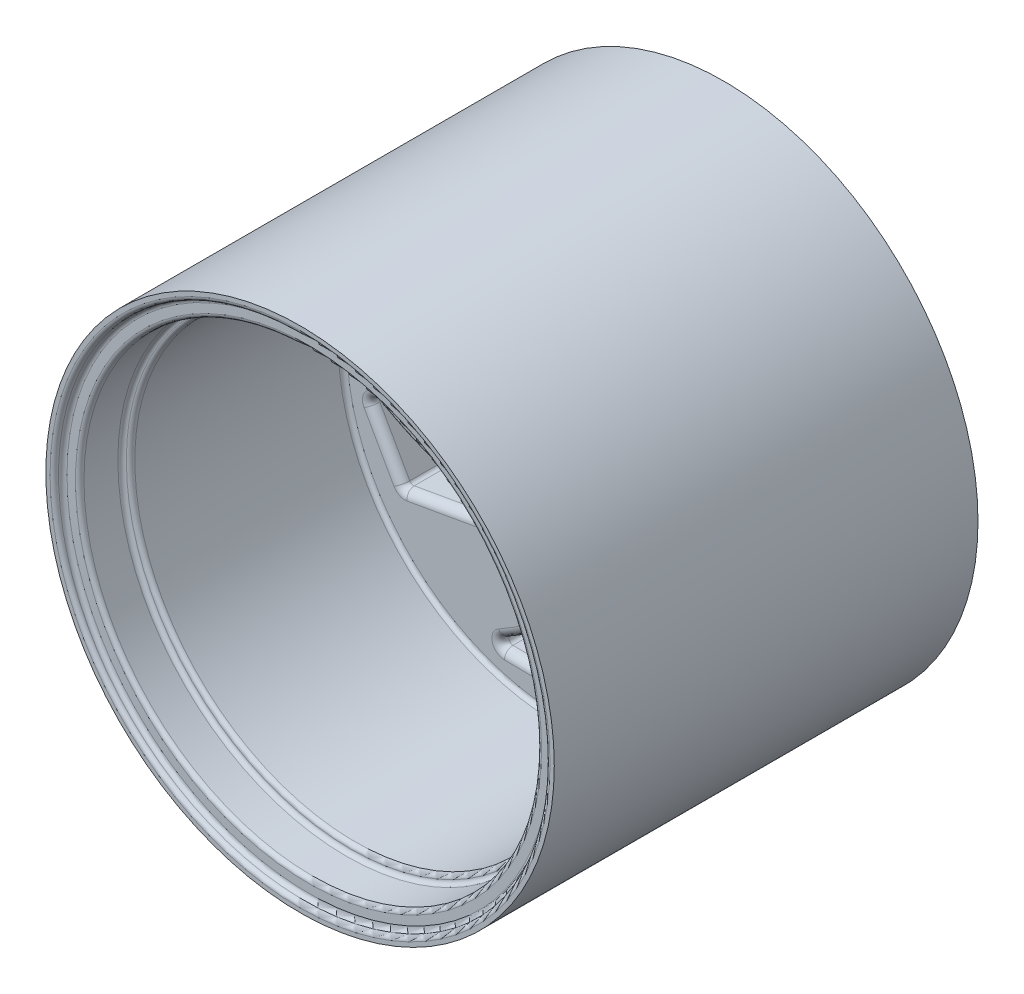
SolidWorks part; units mm, degrees
ref_plane "Ön Düzlem" through (0, 0, 0) normal (0, 0, 1) x (1, 0, 0)
ref_plane "Üst Düzlem" through (0, 0, 0) normal (0, 1, 0) x (1, 0, 0)
ref_plane "Sağ Düzlem" through (0, 0, 0) normal (1, 0, 0) x (0, 0, -1)
sketch "Çizim1" plane through (0, 0, 0) normal (0, 0, 1) x (1, 0, 0)
  circle A0 centre (-8.1488, -1.5541) radius 30
  dimension "D1" = 60
extrude "Yükseklik-Ekstrüzyon1" add sketch "Çizim1" along normal blind 50
sketch "Çizim2" plane through (0, 0, 0) normal (0, 0, -1) x (-1, 0, 0)
  circle A0 centre (8.1488, -1.5541) radius 29
  circle A1 centre (8.1488, -1.5541) radius 30 construction
  dimension "D1" = 1
extrude "Kes-Ekstrüzyon1" cut sketch "Çizim2" against normal blind 1
sketch "Çizim3" plane through (0, 0, 50) normal (0, 0, 1) x (1, 0, 0)
  circle A0 centre (-8.1488, -1.5541) radius 29
  circle A1 centre (-8.1488, -1.5541) radius 30 construction
  dimension "D1" = 1
extrude "Kes-Ekstrüzyon2" cut sketch "Çizim3" against normal blind 1
sketch "Çizim4" plane through (0, 0, 49) normal (0, 0, 1) x (1, 0, 0)
  circle A0 centre (-8.1488, -1.5541) radius 27
  circle A1 centre (-8.1488, -1.5541) radius 29 construction
  dimension "D1" = 2
extrude "Kes-Ekstrüzyon3" cut sketch "Çizim4" against normal blind 5
sketch "Çizim5" plane through (0, 0, 44) normal (0, 0, 1) x (1, 0, 0)
  circle A0 centre (-8.1488, -1.5541) radius 26
  circle A1 centre (-8.1488, -1.5541) radius 27 construction
  dimension "D1" = 1
extrude "Kes-Ekstrüzyon4" cut sketch "Çizim5" against normal blind 25
sketch "Çizim6" plane through (0, 0, 19) normal (0, 0, 1) x (1, 0, 0)
  circle A0 centre (-8.1488, -1.5541) radius 10
  circle A1 centre (-8.1488, -1.5541) radius 8
  circle A2 centre (-8.1488, 4.4459) radius 1
  circle A3 centre (-3.9061, 2.6885) radius 1
  circle A4 centre (-2.1488, -1.5541) radius 1
  circle A5 centre (-3.9061, -5.7967) radius 1
  circle A6 centre (-8.1488, -7.5541) radius 1
  circle A7 centre (-12.3914, -5.7967) radius 1
  circle A8 centre (-14.1488, -1.5541) radius 1
  circle A9 centre (-12.3914, 2.6885) radius 1
  point P23 (-8.1488, -1.5541)
  dimension "D1" = 20
  dimension "D2" = 2
  dimension "D3" = 2
  dimension "D4" = 6
  dimension "D5" = 8
ref_axis "Eksen1" through (-8.1488, -1.5541, 50) along (0, 0, -1)
extrude "Yükseklik-Ekstrüzyon2" add sketch "Çizim6" along normal blind 2 contours A0 A1 | A2 | A8 | A7 | A6 | A5 | A3 | A9 | A4 region at (-17.8659, -1.5541, 19) region at (-8.1488, 4.4459, 19) region at (-3.9061, 2.6885, 19) region at (-3.9061, -5.7967, 19) region at (-8.1488, -7.5541, 19) region at (-12.3914, -5.7967, 19) region at (-14.1488, -1.5541, 19)
sketch "Çizim8" plane through (0, 0, 19) normal (0, 0, 1) x (1, 0, 0)
  circle A0 centre (-8.1488, -1.5541) radius 2
  dimension "D1" = 4
extrude "Kes-Ekstrüzyon5" cut sketch "Çizim8" against normal through all
sketch "Çizim9" plane through (0, 0, 19) normal (0, 0, 1) x (1, 0, 0)
  line L0 (-13.9257, 6.6084) -> (-8.8336, 20.6384)
  line L1 (-8.8336, 20.6384) -> (0.7231, 20.5255)
  line L3 (-3.9683, 7.5301) -> (10.7281, 10.1352)
  line L4 (10.7281, 10.1352) -> (15.4086, 1.8024)
  line L5 (1.8086, -0.6324) -> (11.4129, -12.0573)
  line L6 (11.4129, -12.0573) -> (6.5368, -20.2771)
  line L7 (-2.3718, -9.7166) -> (-7.464, -23.7466)
  line L8 (-7.464, -23.7466) -> (-17.0206, -23.6337)
  line L9 (-12.3293, -10.6383) -> (-27.0257, -13.2434)
  line L10 (-27.0257, -13.2434) -> (-31.7062, -4.9106)
  line L11 (-18.1062, -2.4758) -> (-27.7105, 8.9491)
  line L12 (-30.8072, 6.6742) -> (-25.9311, 14.894) [skipped]
  line L13 (-21.203, -4.7508) -> (-30.8072, 6.6742) [skipped]
  line L14 (-29.7006, -19.3377) -> (-34.3811, -11.0049) [skipped]
  line L15 (-15.0042, -16.7326) -> (-29.7006, -19.3377) [skipped]
  line L16 (-1.5282, -17.3553) -> (-6.6204, -31.3853) [skipped]
  line L17 (-6.6204, -31.3853) -> (-16.177, -31.2724) [skipped]
  line L18 (5.749, -5.9961) -> (15.3533, -17.421) [skipped]
  line L19 (15.3533, -17.421) -> (10.4771, -25.6408) [skipped]
  line L20 (-0.4498, 5.9858) -> (14.2467, 8.5908) [skipped]
  line L21 (14.2467, 8.5908) -> (18.9272, 0.2581) [skipped]
  line L22 (-27.7105, 8.9491) -> (-22.8343, 17.1689)
  circle A0 centre (-8.1488, -1.5541) radius 10 construction
  spline S0 degree 2 poles (0.7231, 20.5255) (-8.7276, 15.9675) (-13.9257, 6.6084) knots 0 0 0 1 1 1
  spline S1 degree 2 poles (15.4086, 1.8024) (6.7359, 7.708) (-3.9683, 7.5301) knots 0 0 0 1 1 1
  spline S2 degree 2 poles (6.5368, -20.2771) (7.3147, -9.8136) (1.8086, -0.6324) knots 0 0 0 1 1 1
  spline S3 degree 2 poles (-17.0206, -23.6337) (-7.5699, -19.0756) (-2.3718, -9.7166) knots 0 0 0 1 1 1
  spline S4 degree 2 poles (-31.7062, -4.9106) (-23.0335, -10.8162) (-12.3293, -10.6383) knots 0 0 0 1 1 1
  spline S5 degree 2 poles (-22.8343, 17.1689) (-23.6123, 6.7054) (-18.1062, -2.4758) knots 0 0 0 1 1 1
  point P29 (-7.727, -5.3734)
  point P55 (-8.1488, -1.5541)
  dimension "D1" = 6
  dimension "D2" = 6
extrude "Kes-Ekstrüzyon6" cut sketch "Çizim9" against normal through all
sketch "Çizim12" plane through (0, 0, 1) normal (0, 0, -1) x (-1, 0, 0)
  circle A0 centre (8.1488, -1.5541) radius 29
extrude "Kes-Ekstrüzyon7" cut sketch "Çizim12" against normal blind 10
sketch "Çizim13" plane through (0, 0, 11) normal (0, 0, -1) x (-1, 0, 0)
  line L0 (25.695, 21.5369) -> (26.0905, 21.2309)
  line L1 (13.3589, -5.1856) -> (13.8988, 1.1423)
  line L2 (13.8988, 1.1423) -> (8.6887, 4.7738)
  line L3 (8.6887, 4.7738) -> (2.9386, 2.0774)
  line L4 (2.9386, 2.0774) -> (2.3988, -4.2505)
  line L5 (2.3988, -4.2505) -> (7.6089, -7.882)
  line L6 (7.6089, -7.882) -> (13.3589, -5.1856)
  line L7 (13.239, 4.6176) -> (26.0905, 21.2309)
  line L8 (12.8435, 4.9235) -> (25.695, 21.5369)
  line L9 (16.1059, -2.3811) -> (36.9193, -5.2041)
  line L10 (16.0387, -2.8765) -> (36.8521, -5.6996)
  line L11 (36.9193, -5.2041) -> (36.8521, -5.6996)
  line L12 (11.4112, -8.8587) -> (19.373, -28.2951)
  line L13 (10.9485, -9.0482) -> (18.9103, -28.4846)
  line L14 (19.373, -28.2951) -> (18.9103, -28.4846)
  line L15 (3.454, -8.0317) -> (-9.3975, -24.6451)
  line L16 (3.0585, -7.7258) -> (-9.7929, -24.3391)
  line L17 (-9.3975, -24.6451) -> (-9.7929, -24.3391)
  line L18 (0.1916, -0.7271) -> (-20.6217, 2.0959)
  line L19 (0.2588, -0.2317) -> (-20.5545, 2.5914)
  line L20 (-20.6217, 2.0959) -> (-20.5545, 2.5914)
  line L21 (4.8864, 5.7505) -> (-3.0755, 25.1869)
  line L22 (5.3491, 5.94) -> (-2.6128, 25.3764)
  line L23 (-3.0755, 25.1869) -> (-2.6128, 25.3764)
  circle A0 centre (8.1488, -1.5541) radius 5.5 construction
  arc A1 (4.8864, 5.7505) -> (0.2588, -0.2317) centre (8.1488, -1.5541) ccw
  arc A2 (12.8435, 4.9235) -> (5.3491, 5.94) centre (8.1488, -1.5541) ccw
  arc A3 (0.1916, -0.7271) -> (3.0585, -7.7258) centre (8.1488, -1.5541) ccw
  arc A4 (3.454, -8.0317) -> (10.9485, -9.0482) centre (8.1488, -1.5541) ccw
  arc A5 (11.4112, -8.8587) -> (16.0387, -2.8765) centre (8.1488, -1.5541) ccw
  arc A6 (16.1059, -2.3811) -> (13.239, 4.6176) centre (8.1488, -1.5541) ccw
  point P37 (8.1488, -1.5541)
  dimension "D2" = 16
  dimension "D1" = 11
  dimension "D3" = 0.5
  dimension "D4" = 6
extrude "Yükseklik-Ekstrüzyon4" add sketch "Çizim13" along normal blind 10
fillet "Radyus1" radius 0.5 6 edges at (17.8512, -1.5541, 19) (20.8512, -1.5541, 50) (20.8512, -1.5541, 49) (18.8512, -1.5541, 49) (18.8512, -1.5541, 44) (17.8512, -1.5541, 44)
fillet "Radyus5" radius 0.5 18 edges at (-22.8343, 17.1689, 15) (-18.1062, -2.4758, 15) (-27.7105, 8.9491, 15) (-12.3293, -10.6383, 15) (-27.0257, -13.2434, 15) (-31.7062, -4.9106, 15) (-17.0206, -23.6337, 15) (-2.3718, -9.7166, 15) (-7.464, -23.7466, 15) (6.5368, -20.2771, 15) (1.8086, -0.6324, 15) (11.4129, -12.0573, 15) (-3.9683, 7.5301, 15) (15.4086, 1.8024, 15) (10.7281, 10.1352, 15) (0.7231, 20.5255, 15) (-13.9257, 6.6084, 15) (-8.8336, 20.6384, 15)
fillet "Radyus6" radius 1 36 edges at (14.3408, 2.944, 19) (12.6652, 6.6867, 19) (10.6798, 10.0329, 19) (5.4279, 9.1957, 19) (0.0646, 7.8091, 19) (-0.7995, 20.1716, 19) (-4.8785, 20.5917, 19) (-8.7692, 20.5454, 19) (-10.67, 15.5786, 19) (-12.1509, 10.2405, 19) (-23.2891, 15.6734, 19) (-25.6925, 12.3509, 19) (-27.5977, 8.9584, 19) (-24.2467, 4.8288, 19) (-20.3643, 0.8773, 19) (-30.6384, -6.0522, 19) (-28.9627, -9.7949, 19) (-26.9773, -13.1411, 19) (-21.7255, -12.3039, 19) (-16.3622, -10.9173, 19) (4.0667, -3.9855, 19) (7.9491, -7.937, 19) (11.3001, -12.0666, 19) (9.3949, -15.4591, 19) (6.9915, -18.7816, 19) (-4.1467, -13.3487, 19) (-5.6275, -18.6867, 19) (-7.5284, -23.6536, 19) (-11.419, -23.6999, 19) (-15.4981, -23.2798, 19)
fillet "Radyus7" radius 0.5 25 edges at (-17.233, 2.6264, 19) (-16.3113, -7.331, 19) (-7.2271, -11.5115, 19) (0.9355, -5.7346, 19) (0.0137, 4.2228, 19) (-9.0705, 8.4033, 19) (-2.9061, -5.7967, 21) (-11.3914, 2.6885, 21) (-11.3914, -5.7967, 19) (-13.1488, -1.5541, 19) (-11.3914, -5.7967, 21) (-7.1488, -7.5541, 19) (-7.1488, -7.5541, 21) (-2.9061, -5.7967, 19) (-1.1488, -1.5541, 19) (-1.1488, -1.5541, 21) (-2.9061, 2.6885, 21) (-7.1488, 4.4459, 19) (-2.9061, 2.6885, 19) (-0.1488, -1.5541, 19) (-7.1488, 4.4459, 21) (-11.3914, 2.6885, 19) (-13.1488, -1.5541, 21) (-0.1488, -1.5541, 21) (1.8512, -1.5541, 21)
sketch "Sketch1" plane through (0, 0, 11) normal (0, 0, -1) x (-1, 0, 0)
  line L1 (8.6887, 4.7738) -> (2.9386, 2.0774)
  line L2 (2.9386, 2.0774) -> (2.3988, -4.2505)
  line L3 (2.3988, -4.2505) -> (7.6089, -7.882)
  line L4 (7.6089, -7.882) -> (13.3589, -5.1856)
  line L5 (13.3589, -5.1856) -> (13.8988, 1.1423)
  line L6 (13.8988, 1.1423) -> (8.6887, 4.7738)
  circle A0 centre (8.1488, -1.5541) radius 5.5 construction
  circle A1 centre (8.1488, -1.5541) radius 2
  dimension "D1" = 11
extrude "Boss-Extrude1" add sketch "Sketch1" along normal blind 2
